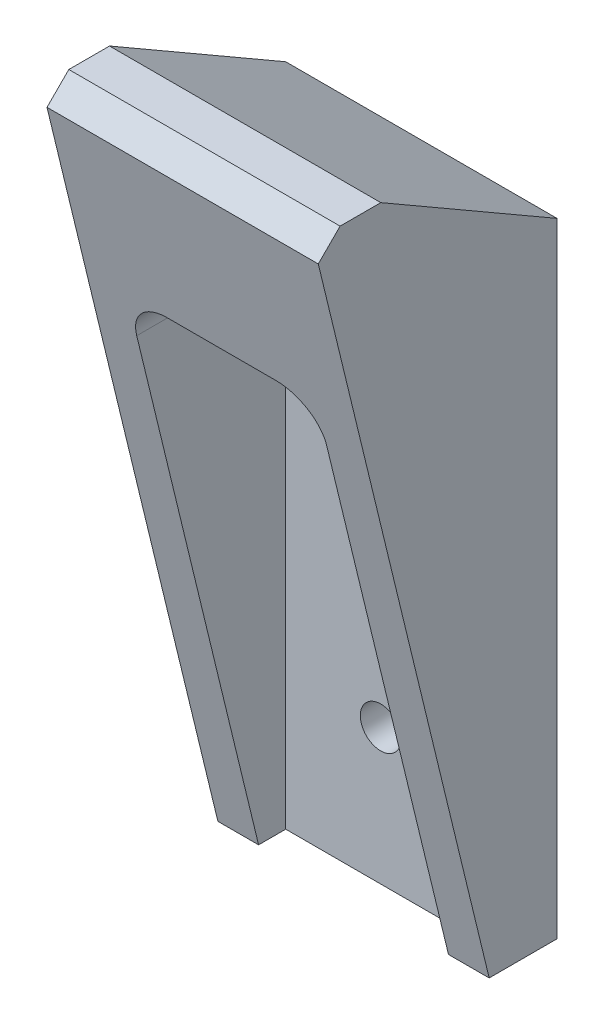
SolidWorks part; units mm, degrees
ref_plane "Front Plane" through (0, 0, 0) normal (0, 0, 1) x (1, 0, 0)
ref_plane "Top Plane" through (0, 0, 0) normal (0, 1, 0) x (1, 0, 0)
ref_plane "Right Plane" through (0, 0, 0) normal (1, 0, 0) x (0, 0, -1)
sketch "Sketch1" plane through (0, 0, 0) normal (1, 0, 0) x (0, 0, -1)
  line L0 (0, 0) -> (-5, 0)
  line L1 (0, 0) -> (0, 46)
  line L2 (0, 46) -> (-12.9904, 53.5)
  line L3 (-12.9904, 53.5) -> (-17.9904, 53.5)
  line L4 (-17.9904, 53.5) -> (-5, 0)
  dimension "D1" = 5
  dimension "D2" = 46
  dimension "D3" = 120
  dimension "D4" = 15
  dimension "D5" = 5
extrude "Boss-Extrude1" add sketch "Sketch1" along normal blind 20
ref_plane "Plane1" through (0, 0, 0) normal (0, -1, 0) x (-1, 0, 0)
ref_point "Point1"
ref_plane "Plane2" through (0, 0, 17.9904) normal (0, 0, 1) x (1, 0, 0)
sketch "Sketch4" plane through (0, 0, 17.9904) normal (0, 0, 1) x (1, 0, 0)
  line L0 (10, 0) -> (10, 53.5) construction
  line L1 (0, 0) -> (3, 0)
  line L2 (20, 0) -> (17, 0)
  line L3 (3, 0) -> (3, 40)
  line L4 (0, 53.5) -> (0, 0)
  line L5 (0, 0) -> (20, 0)
  line L6 (20, 0) -> (20, 53.5)
  line L7 (20, 53.5) -> (0, 53.5)
  line L8 (0, 53.5) -> (0, 0)
  line L9 (0, 0) -> (20, 0)
  line L10 (20, 0) -> (20, 53.5)
  line L11 (20, 53.5) -> (0, 53.5)
  line L12 (3, 40) -> (17, 40)
  line L13 (17, 40) -> (17, 0)
  dimension "D2" = 3
  dimension "D3" = 3
  dimension "D4" = 40
  dimension "D1" = 0
extrude "Cut-Extrude1" cut sketch "Sketch4" against normal offset from surface (14.9904 mm away) 3 contours L0 L9 L13 L12 | L9 L0 L12 L3 region at (6.5, 20, 17.9904) region at (13.5, 20, 17.9904) up to face at (10, 23, 0)
sketch "Sketch5" plane through (0, 0, 3) normal (0, 0, 1) x (1, 0, 0)
  line L0 (10, 0) -> (10, 53.1114) construction
  line L1 (17, 0) -> (3, 0) construction
  line L2 (17, 40) -> (3, 40) construction
  point P4 (10, 10)
  point P5 (10, 30)
  dimension "D1" = 10
  dimension "D2" = 10
fillet "Fillet1" radius 3 2 edges at (3, 40, 8.8562) (17, 40, 8.8562)
chamfer "Chamfer1" distance 2 angle 45 1 edges at (10, 53.5, 17.9904) first distance on face at (10, 53.5, 15.4904)
hole_wizard "#25 (0.1495) Diameter Hole2" positions "3DSketch2" profile "Sketch8" hole size "#25" standard "ANSI Inch" end condition through all
sketch3d "3DSketch2"
  point P0 (10, 30, 3)
  point P3 (10, 10, 3)
sketch "Sketch8" plane through (10, 30, 3) normal (1, 0, 0) x (0, -1, 0)
  line L0 (0, 0) -> (0, 3)
  line L1 (0, 3) -> (1.5, 3)
  line L2 (1.5, 3) -> (1.5, 0)
  line L5 (1.5, 0) -> (0, 0)
  line L11 (0, -6.35) -> (0, 107.95) construction
  dimension "Thru Hole Dia." = 3
  dimension "Thru Hole Depth" = 3
